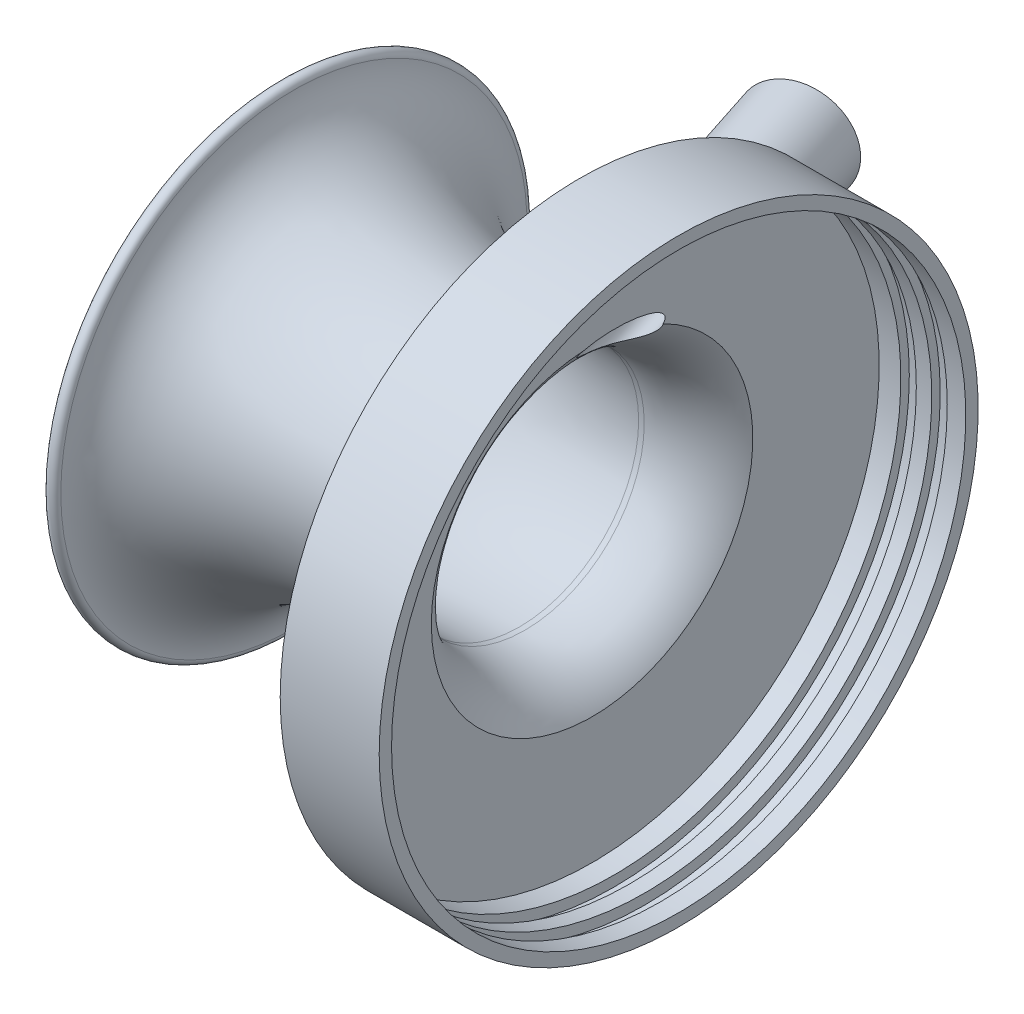
SolidWorks part; units mm, degrees
material "PVC 0.007 Plasticized"
ref_plane "Front Plane" through (0, 0, 0) normal (0, 0, 1) x (1, 0, 0)
ref_plane "Top Plane" through (0, 0, 0) normal (0, 1, 0) x (1, 0, 0)
ref_plane "Right Plane" through (0, 0, 0) normal (1, 0, 0) x (0, 0, -1)
sketch "Sketch1" plane through (0, 0, 0) normal (0, 0, 1) x (1, 0, 0)
  line L0 (-17.78, 33.4033) -> (-17.78, 59.3503)
  line L1 (-34.3222, 33.4033) -> (-9.5791, 33.4033) construction
  line L3 (-34.3222, 0.4033) -> (53.9483, 0.4033) construction
  line L11 (-32.6995, 24.8889) -> (-31.5799, 24.9144)
  line L12 (-17.78, 59.3503) -> (0, 59.3503)
  line L13 (-32.7541, 27.4283) -> (-31.68, 27.4528)
  line L14 (-20.32, 34.1122) -> (-20.32, 61.8903)
  line L15 (-20.32, 61.8903) -> (0, 61.8903)
  line L16 (0, 61.8903) -> (0, 59.3503)
  circle A4 centre (-32.5108, 41.8889) radius 17 construction
  arc A5 (-17.78, 33.4033) -> (-31.5799, 24.9144) centre (-32.5108, 41.8889) cw
  arc A6 (-20.32, 34.1122) -> (-31.68, 27.4528) centre (-32.5108, 41.8889) cw
  arc A7 (-81.5276, 48.209) -> (-78.9882, 48.2636) centre (-80.2579, 48.2363) cw
  ellipse E0 centre (-33.2232, 49.2475) end of major axis (15.0812, 50.2859) minor radius 24.3642 (-81.5276, 48.209) -> (-32.6995, 24.8889) ccw
  ellipse E1 centre (-33.2232, 49.2475) end of major axis (-81.5276, 48.209) minor radius 24.3642 construction
  spline S0 degree 1 poles (-78.9882, 48.2636) (-32.7541, 27.4283) knots 0 0 1 1 construction
  spline S1 degree 3 poles (-78.9882, 48.2636) (-78.9745, 47.627) (-78.8248, 46.3708) (-78.0214, 43.8262) (-76.0087, 40.6014) (-71.877, 36.8457) (-66.142, 33.4811) (-59.043, 30.716) (-50.8772, 28.701) (-42.0017, 27.5355) (-35.8146, 27.3625) (-32.7541, 27.4283) knots 3.141593 3.141593 3.141593 3.141593 3.239767 3.337942 3.534292 3.730641 3.926991 4.12334 4.31969 4.516039 4.712389 4.712389 4.712389 4.712389
  dimension "D3" = 24.3586
  dimension "D1" = 33.0001
  dimension "D2" = 15.4432
  dimension "D4" = 48.3044
  dimension "D5" = 58.947
  dimension "D10" = 34
  dimension "D11" = 17
  dimension "D12" = 31.5799
  dimension "D9" = 1.27
  dimension "D6" = 17.78
  dimension "D8" = 24.4856
  dimension "D7" = 2.54
  dimension "D13" = 31.68
  dimension "D14" = 34.3222
  dimension "D15" = 0.4033
revolve "Revolve1" add sketch "Sketch1" angle 360 about L3
ref_axis "Axis1" through (0, 65.659, 0) along (0, -1, 0)
ref_plane "Plane1" through (0, 0, 0) normal (-0.309, 0, -0.9511) x (0, -1, 0)
ref_plane "Plane2" through (-13.3434, 0, -41.0666) normal (-0.309, 0, -0.9511) x (0, -1, 0)
sketch "Sketch2" plane through (-13.3434, 0, -41.0666) normal (-0.309, 0, -0.9511) x (0, -1, 0)
  line L0 (-33.0001, 18.6255) -> (-26.9006, 18.6255) construction
  circle A0 centre (-30.8893, 15.4505) radius 3.175
  circle A1 centre (-30.8893, 15.4505) radius 10.16
  circle A2 centre (-30.8893, 15.4505) radius 5.5562
  ellipse E0 centre (0, 18.6255) end of major axis (-33.0001, 18.6255) minor radius 9.0224 construction
  dimension "D1" = 6.35
  dimension "D2" = 20.32
  dimension "D3" = 11.1125
  dimension "D4" = 0
extrude "Boss-Extrude1" add sketch "Sketch2" against normal up to next separate body contours A2 A0 region at (-28.0376, 36.2884, -36.2922)
extrude "Cut-Extrude1" cut sketch "Sketch2<3>" along direction (-0.309, 0, -0.9511) on the side against the normal blind 40.64 and the other way through all contours A0 region at (-28.0376, 30.8893, -36.2922)
sketch "Sketch2<3>" plane through (-13.3434, 0, -41.0666) normal (-0.309, 0, -0.9511) x (0, -1, 0) same geometry as "Sketch2"
extrude "Boss-Extrude3" add sketch "Sketch2<4>" against normal blind 1.016 and the other way blind 25.4 contours A1 A2 region at (-28.0376, 40.7619, -36.2922)
sketch "Sketch2<4>" plane through (-13.3434, 0, -41.0666) normal (-0.309, 0, -0.9511) x (0, -1, 0) same geometry as "Sketch2"
sketch "Sketch5" plane through (0, 0, 0) normal (0, 0, 1) x (1, 0, 0)
  line L0 (-10.16, 60.6838) -> (-13.335, 60.6838)
  line L1 (-10.16, 60.6838) -> (-10.16, 59.0963)
  line L2 (-13.335, 60.6838) -> (-13.335, 59.0963)
  line L4 (0, 0) -> (-88.0301, 0) construction
  line L5 (-13.335, 59.0963) -> (-13.335, 57.8263)
  line L7 (-10.16, 57.8263) -> (-10.16, 59.0963)
  line L14 (-13.335, 57.8263) -> (-10.16, 57.8263)
  line L15 (-3.81, 60.6838) -> (-6.985, 60.6838)
  line L16 (-3.81, 60.6838) -> (-3.81, 59.0963)
  line L17 (-6.985, 60.6838) -> (-6.985, 59.0963)
  line L18 (-6.985, 59.0963) -> (-6.985, 57.8263)
  line L19 (-3.81, 57.8263) -> (-3.81, 59.0963)
  line L20 (-6.985, 57.8263) -> (-3.81, 57.8263)
  line L21 (-20.32, 61.8903) -> (-20.32, -61.0838) construction
  line L22 (-20.32, 61.8903) -> (-20.32, -61.0838)
  dimension "D1" = 1.5875
  dimension "D2" = 59.0963
  dimension "D3" = 3.175
  dimension "D4" = 0
  dimension "D5" = 10.16
  dimension "D6" = 1.27
  dimension "D8" = 1.5875
  dimension "D9" = 3.175
  dimension "D11" = 3.81
revolve "Cut-Revolve2" cut sketch "Sketch5" angle 360 about L4 region at (-11.7475, 59.2551, 0) region at (-5.3975, 59.2551, 0)
